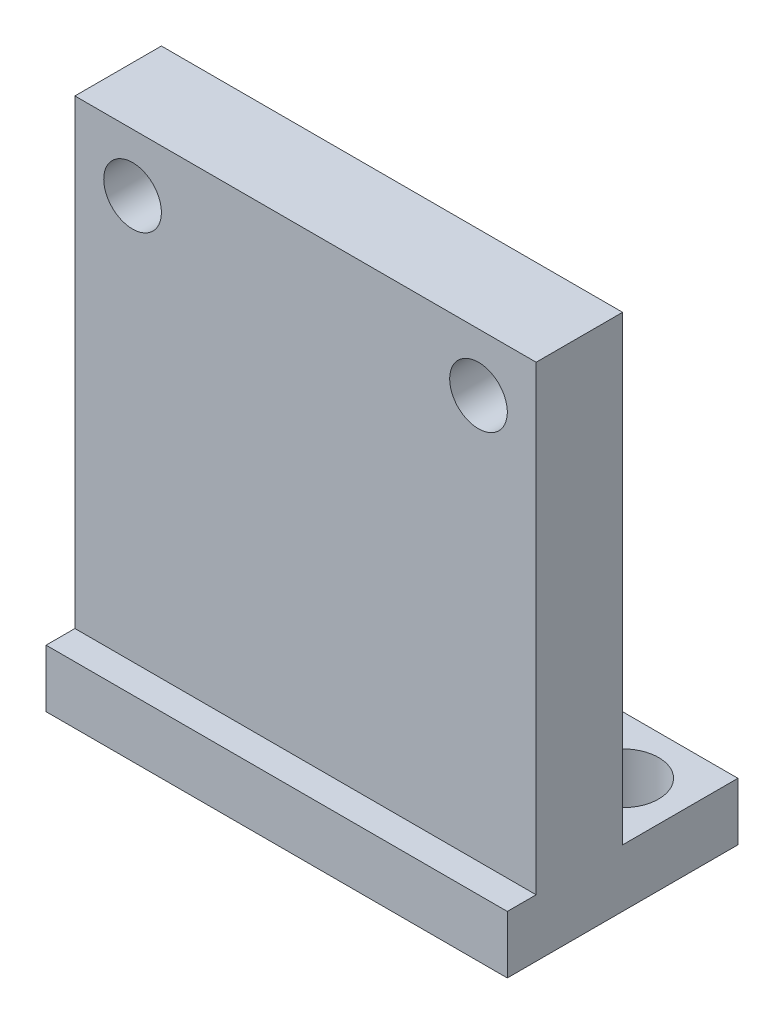
SolidWorks part; units mm, degrees
ref_plane "Front Plane" through (0, 0, 0) normal (0, 0, 1) x (1, 0, 0)
ref_plane "Top Plane" through (0, 0, 0) normal (0, 1, 0) x (1, 0, 0)
ref_plane "Right Plane" through (0, 0, 0) normal (1, 0, 0) x (0, 0, -1)
sketch "Sketch1" plane through (0, 0, 0) normal (0, 0, 1) x (1, 0, 0)
  line L1 (0, 0) -> (20.32, 0)
  line L2 (0, 0) -> (0, 22.86)
  line L3 (0, 22.86) -> (20.32, 22.86)
  line L4 (20.32, 0) -> (20.32, 22.86)
  dimension "D1" = 20.32
  dimension "D2" = 22.86
extrude "Boss-Extrude1" add sketch "Sketch1" along normal blind 5.08
sketch "Sketch2" plane through (0, 0, 5.08) normal (0, 0, 1) x (1, 0, 0)
  line L1 (0, 22.86) -> (0, 0) construction
  line L2 (20.32, 22.86) -> (0, 22.86) construction
  circle A0 centre (2.54, 20.32) radius 1.27
  circle A1 centre (17.78, 20.32) radius 1.27
  point P4 (0, 0)
  dimension "D4" = 2.54
  dimension "D1" = 15.24
  dimension "D2" = 2.54
  dimension "D3" = 2.54
extrude "Cut-Extrude1" cut sketch "Sketch2" against normal up to next
sketch "Sketch3" plane through (0, 0, 0) normal (0, -1, 0) x (1, 0, 0)
  line L0 (20.32, 5.08) -> (20.32, 0) construction
  line L1 (0, 5.08) -> (20.32, 5.08)
  line L2 (0, 5.08) -> (0, -5.08)
  line L3 (0, -5.08) -> (20.32, -5.08)
  line L4 (20.32, 5.08) -> (20.32, -5.08)
  dimension "D1" = 10.16
extrude "Boss-Extrude2" add sketch "Sketch3" against normal blind 2.54
sketch "Sketch4" plane through (0, 0, 5.08) normal (0, 0, 1) x (1, 0, 0)
  line L0 (0, 22.86) -> (0, 0) construction
  line L1 (20.32, 22.86) -> (0, 22.86)
  line L2 (20.32, 22.86) -> (20.32, 2.54)
  line L3 (20.32, 2.54) -> (0, 2.54)
  line L4 (0, 22.86) -> (0, 2.54)
  line L5 (0, 0) -> (20.32, 0) construction
  dimension "D1" = 2.54
extrude "Cut-Extrude2" cut sketch "Sketch4" against normal blind 1.27
sketch "Sketch5" plane through (0, 2.54, 0) normal (0, 1, 0) x (1, 0, 0)
  line L0 (20.32, 5.08) -> (20.32, 0) construction
  line L1 (0, 0) -> (0, 5.08) construction
  line L2 (20.32, 0) -> (0, 0) construction
  circle A0 centre (17.78, 2.54) radius 1.5875
  circle A1 centre (2.54, 2.54) radius 1.5875
  point P4 (0, 0)
  dimension "D1" = 3.175
  dimension "D2" = 2.54
  dimension "D3" = 2.54
  dimension "D4" = 2.54
extrude "Cut-Extrude3" cut sketch "Sketch5" against normal blind 2.54
